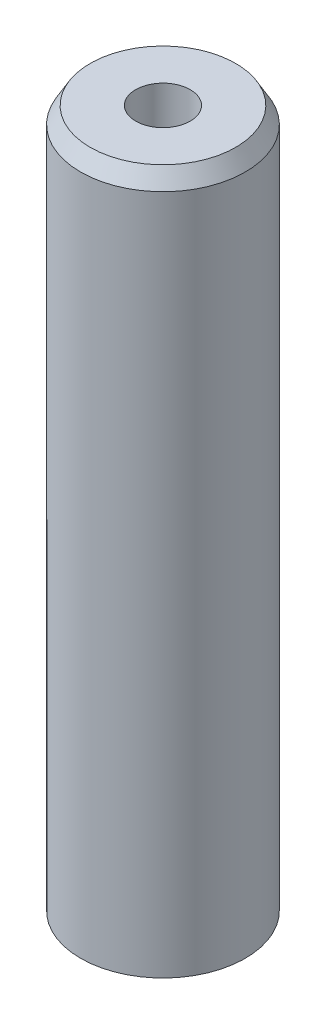
SolidWorks part; units mm, degrees
ref_plane "Front Plane" through (0, 0, 0) normal (0, 0, 1) x (1, 0, 0)
ref_plane "Top Plane" through (0, 0, 0) normal (0, 1, 0) x (1, 0, 0)
ref_plane "Right Plane" through (0, 0, 0) normal (1, 0, 0) x (0, 0, -1)
sketch "Sketch1" plane through (0, 0, 0) normal (0, 1, 0) x (1, 0, 0)
  circle A0 centre (0, 0) radius 15
  dimension "SHAFT_OD" = 30
extrude "Boss-Extrude1" add sketch "Sketch1" along normal blind 128.8511
sketch "Sketch2" plane through (0, 0, 0) normal (0, 1, 0) x (1, 0, 0)
  circle A0 centre (0, 0) radius 4.9733
  dimension "BORE_D" = 9.9466
extrude "Cut-Extrude1" cut sketch "Sketch2" along normal through all
chamfer "Chamfer1" distance 3.0212 angle 30 2 edges at (0, 128.8511, 15) (0, 0, 15) first distance on face at (0, 128.8511, 15) first distance on face at (0, 0, 4.9733)
